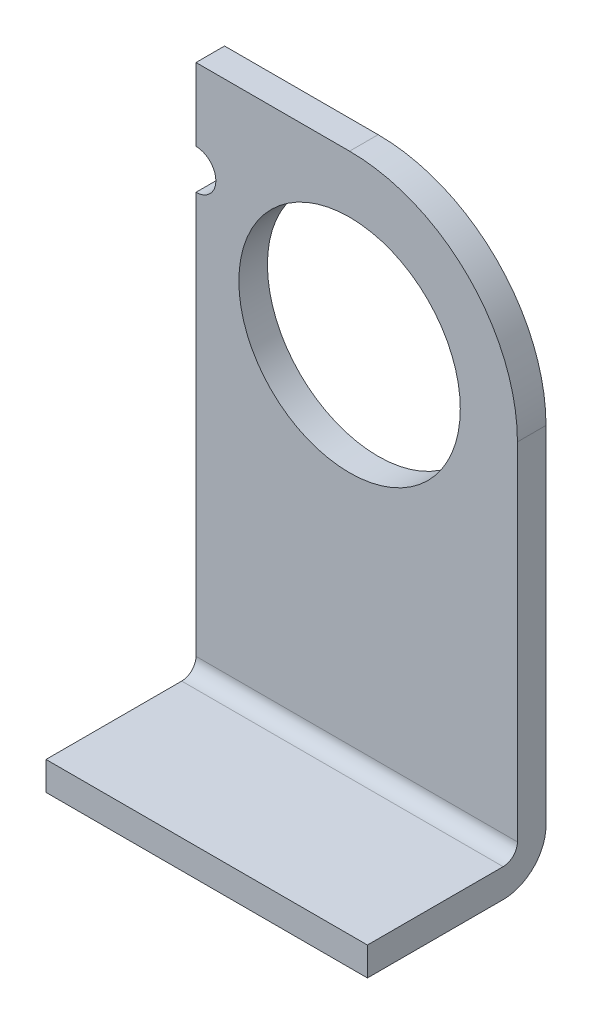
SolidWorks part; units mm, degrees
ref_plane "Front Plane" through (0, 0, 0) normal (0, 0, 1) x (1, 0, 0)
ref_plane "Top Plane" through (0, 0, 0) normal (0, 1, 0) x (1, 0, 0)
ref_plane "Right Plane" through (0, 0, 0) normal (1, 0, 0) x (0, 0, -1)
sketch "Sketch1" plane through (0, 0, 0) normal (0, 1, 0) x (1, 0, 0)
  line L1 (0, 0) -> (22.5, 0)
  line L2 (0, 0) -> (0, 12.5)
  line L3 (0, 12.5) -> (22.5, 12.5)
  line L4 (22.5, 0) -> (22.5, 12.5)
  dimension "D1" = 12.5
  dimension "D2" = 22.5
extrude "Boss-Extrude1" add sketch "Sketch1" along normal blind 2
sketch "Sketch2" plane through (0, 0, -12.5) normal (0, 0, -1) x (-1, 0, 0)
  line L1 (-22.5, 2) -> (0, 2)
  line L2 (-22.5, 2) -> (-22.5, 39)
  line L3 (-22.5, 39) -> (0, 39)
  line L4 (0, 2) -> (0, 39)
  dimension "D1" = 37
extrude "Boss-Extrude2" add sketch "Sketch2" against normal blind 2
fillet "Fillet1" radius 1 1 edges at (11.25, 2, -10.5)
fillet "Fillet2" radius 3 1 edges at (11.25, 0, -12.5)
sketch "Sketch5" plane through (0, 0, -12.5) normal (0, 0, -1) x (-1, 0, 0)
  line L1 (-22.5, 39) -> (-22.5, 3) construction
  line L2 (0, 39) -> (-22.5, 39) construction
  circle A0 centre (-10.75, 27.25) radius 7.75
  dimension "D1" = 4
  dimension "D2" = 4
  dimension "D3" = 15.5
extrude "Cut-Extrude1" cut sketch "Sketch5" against normal blind 2 contours A0
sketch "Sketch6" plane through (0, 0, -12.5) normal (0, 0, -1) x (-1, 0, 0)
  line L0 (-22.5, 39) -> (-22.5, 3) construction
  line L1 (0, 39) -> (-22.5, 39) construction
  arc A0 (-22.5, 27.25) -> (-10.75, 39) centre (-10.75, 27.25) cw
extrude "Cut-Extrude2" cut sketch "Sketch6" against normal blind 2 and the other way through all
sketch "Sketch7" plane through (0, 0, -12.5) normal (0, 0, -1) x (-1, 0, 0)
  line L0 (0, 39) -> (0, 3) construction
  arc A0 (0, 33.9127) -> (0, 31.1339) centre (0, 32.5233) ccw
extrude "Cut-Extrude3" cut sketch "Sketch7" against normal blind 2 and the other way through all
